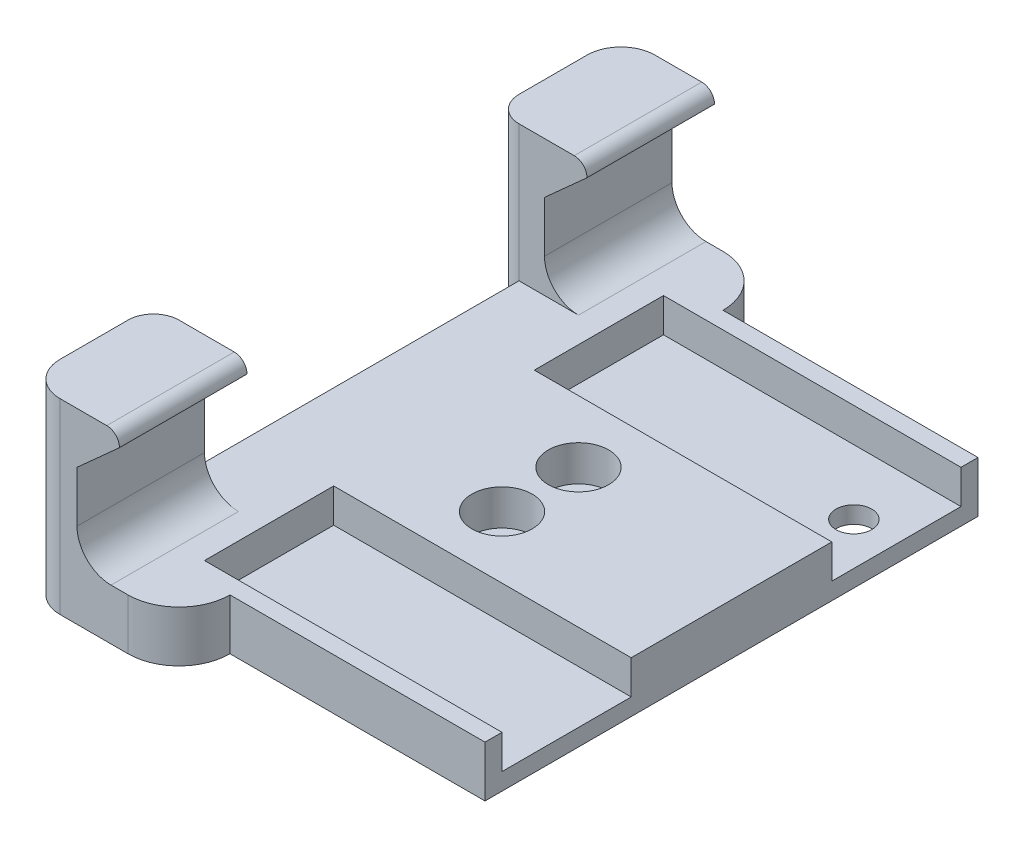
SolidWorks part; units mm, degrees
ref_plane "Plan de face" through (0, 0, 0) normal (0, 0, 1) x (1, 0, 0)
ref_plane "Plan de dessus" through (0, 0, 0) normal (0, 1, 0) x (1, 0, 0)
ref_plane "Plan de droite" through (0, 0, 0) normal (1, 0, 0) x (0, 0, -1)
sketch "Esquisse1" plane through (0, 0, 0) normal (0, 0, 1) x (1, 0, 0)
  line L0 (-16.669, 33.1815) -> (-16.669, 15.1815)
  line L1 (-16.669, 15.1815) -> (-1.669, 15.1815)
  line L2 (-1.669, 15.1815) -> (-1.669, 21.1815)
  line L3 (-1.669, 21.1815) -> (-9.669, 21.1815)
  line L4 (-13.669, 25.1815) -> (-13.669, 31.1815)
  line L5 (-13.669, 37.1815) -> (-14.669, 37.1815)
  line L6 (-16.669, 34.1815) -> (-16.669, 33.1815)
  line L7 (-13.669, 37.1815) -> (-10.169, 37.1815)
  line L10 (-14.669, 37.1815) -> (-16.669, 37.1815)
  line L11 (-16.669, 37.1815) -> (-16.669, 34.1815)
  line L12 (-8.669, 35.6815) -> (-13.669, 31.1815)
  arc A1 (-10.169, 37.1815) -> (-8.669, 35.6815) centre (-10.169, 35.6815) cw
  arc A3 (-9.669, 21.1815) -> (-13.669, 25.1815) centre (-9.669, 25.1815) cw
  dimension "D1" = 3
  dimension "D2" = 1.5
  dimension "D4" = 4
  dimension "D6" = 15
  dimension "D7" = 6
extrude "Boss.-Extru.1" add sketch "Esquisse1" along normal blind 70
sketch "Esquisse3" plane through (-16.669, 0, 0) normal (-1, 0, 0) x (0, 0, 1)
  line L0 (70, 37.1815) -> (0, 37.1815) construction
  line L1 (15, 37.1815) -> (55, 37.1815)
  line L2 (15, 37.1815) -> (15, 21.1815)
  line L3 (15, 21.1815) -> (55, 21.1815)
  line L4 (55, 37.1815) -> (55, 21.1815)
  line L5 (0, 37.1815) -> (0, 15.1815) construction
  line L6 (70, 37.1815) -> (70, 15.1815) construction
  line L7 (70, 15.1815) -> (0, 15.1815) construction
  dimension "D1" = 15
  dimension "D2" = 15
  dimension "D3" = 6
extrude "Enlèv. mat.-Extru.1" cut sketch "Esquisse3" against normal blind 15
fillet "Congé2" radius 6 2 edges at (-1.669, 18.1815, 70) (-1.669, 18.1815, 0)
sketch "Esquisse4" plane through (-1.669, 0, 0) normal (1, 0, 0) x (0, 0, -1)
  line L0 (-64, 21.1815) -> (-6, 21.1815) construction
  line L1 (-62, 21.1815) -> (-46.8, 21.1815)
  line L3 (-62, 15.1815) -> (-46.8, 15.1815)
  line L5 (-64, 15.1815) -> (-6, 15.1815) construction
  line L9 (-23.2, 15.1815) -> (-8, 15.1815)
  line L12 (-64, 21.1815) -> (-6, 21.1815)
  line L13 (-64, 21.1815) -> (-64, 15.1815)
  line L14 (-64, 15.1815) -> (-6, 15.1815)
  line L15 (-6, 21.1815) -> (-6, 15.1815)
extrude "Boss.-Extru.2" add sketch "Esquisse4" along normal blind 30
sketch "Esquisse5" plane through (0, 15.1815, 0) normal (0, -1, 0) x (1, 0, 0)
  line L0 (28.331, 35) -> (-16.669, 35) construction
  line L1 (28.331, 64) -> (28.331, 6) construction
  line L2 (-16.669, 70) -> (-16.669, 0) construction
  line L3 (-16.669, 35) -> (5.831, 35) construction
  line L4 (5.831, 35) -> (5.831, 54.864) construction
  line L5 (28.331, 64) -> (-1.669, 64) construction
  circle A0 centre (5.831, 39.5) radius 2.1
  circle A1 centre (5.831, 30.5) radius 2.1
  dimension "D1" = 4.2
  dimension "D2" = 24.5
  dimension "D3" = 9
extrude "Enlèv. mat.-Extru.2" cut sketch "Esquisse5" against normal up to next
sketch "Esquisse6" plane through (0, 21.1815, 0) normal (0, 1, 0) x (1, 0, 0)
  circle A0 centre (5.831, -30.5) radius 3.55
  circle A1 centre (5.831, -39.5) radius 3.55
  dimension "D1" = 7.1
extrude "Enlèv. mat.-Extru.3" cut sketch "Esquisse6" against normal blind 4.2
sketch "Esquisse8" plane through (28.331, 0, 0) normal (1, 0, 0) x (0, 0, -1)
  line L0 (-6, 21.1815) -> (-64, 21.1815) construction
  line L1 (-62, 21.1815) -> (-46.8, 21.1815)
  line L2 (-62, 21.1815) -> (-62, 17.1815)
  line L3 (-62, 17.1815) -> (-46.8, 17.1815)
  line L4 (-46.8, 21.1815) -> (-46.8, 17.1815)
  line L5 (-64, 15.1815) -> (-6, 15.1815) construction
  line L6 (-64, 21.1815) -> (-64, 15.1815) construction
  line L7 (-35, 21.1815) -> (-35, 15.1815) construction
  line L8 (-8, 17.1815) -> (-23.2, 17.1815)
  line L9 (-23.2, 21.1815) -> (-23.2, 17.1815)
  line L10 (-8, 21.1815) -> (-23.2, 21.1815)
  line L11 (-8, 21.1815) -> (-8, 17.1815)
  point P6 (-62, 19.1815)
  dimension "D1" = 15.2
  dimension "D2" = 2
  dimension "D3" = 2
extrude "Enlèv. mat.-Extru.5" cut sketch "Esquisse8" against normal blind 35
sketch "Esquisse9" plane through (0, 17.1815, 0) normal (0, 1, 0) x (1, 0, 0)
  line L0 (28.331, -23.2) -> (28.331, -8) construction
  circle A0 centre (23.331, -15.6045) radius 2.1
  dimension "D1" = 4.2
  dimension "D2" = 5
extrude "Enlèv. mat.-Extru.6" cut sketch "Esquisse9" against normal up to next
sketch "Esquisse10" plane through (0, 15.1815, 0) normal (0, -1, 0) x (1, 0, 0)
  line L0 (-16.669, 70) -> (-16.669, 0) construction
  line L1 (-19.669, 70) -> (-16.669, 70)
  line L2 (-19.669, 70) -> (-19.669, 55)
  line L3 (-19.669, 55) -> (-16.669, 55)
  line L4 (-16.669, 70) -> (-16.669, 55)
  line L5 (-16.669, 70) -> (-7.669, 70) construction
  line L6 (28.331, 35) -> (-40.7947, 35) construction
  line L7 (28.331, 64) -> (28.331, 6) construction
  line L8 (-19.669, 15) -> (-16.669, 15)
  line L9 (-16.669, 0) -> (-16.669, 15)
  line L10 (-19.669, 0) -> (-16.669, 0)
  line L11 (-19.669, 0) -> (-19.669, 15)
  dimension "D1" = 3
  dimension "D2" = 15
extrude "Boss.-Extru.3" add sketch "Esquisse10" against normal blind 22
fillet "Congé3" radius 3 2 edges at (-19.669, 26.1815, 55) (-19.669, 26.1815, 15)
fillet "Congé4" radius 4 2 edges at (-19.669, 26.1815, 0) (-19.669, 26.1815, 70)
